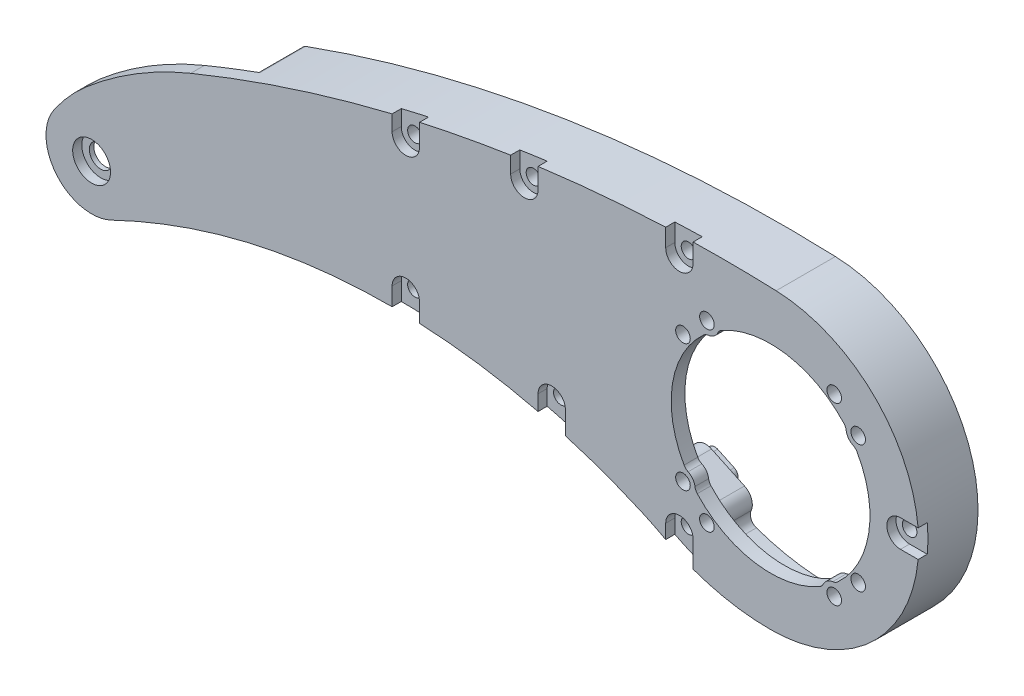
SolidWorks part; units mm, degrees
material "6061-T6 (SS)"
ref_plane "前视基准面" through (0, 0, 0) normal (0, 0, 1) x (1, 0, 0)
ref_plane "上视基准面" through (0, 0, 0) normal (0, 1, 0) x (1, 0, 0)
ref_plane "右视基准面" through (0, 0, 0) normal (1, 0, 0) x (0, 0, -1)
other "Configuration Table"
sketch "草图1" plane through (0, 0, 0) normal (0, 0, 1) x (1, 0, 0)
  line L0 (-74.3846, 0) -> (17.4339, 0) construction
  line L1 (0, 31.8895) -> (0, -25.7876) construction
  line L2 (0, 0) -> (19.2142, 13.9599) construction
  line L3 (0, 0) -> (13.9599, 19.2142) construction
  line L4 (0, 0) -> (-148.9161, -18) construction
  line L6 (0, 0) -> (-1.2281, 22.9672) construction
  line L8 (-1.2281, 22.9672) -> (-150.1441, 4.9672) construction
  line L9 (-150.1441, 4.9672) -> (-148.9161, -18) construction
  line L10 (-148.9161, -18) -> (-97.5528, -158.9319)
  line L12 (0, 0) -> (-103.1063, -167.9797) construction
  arc A116 (16.0762, 14.724) -> (-10.7394, 18.9712) centre (0, 0) ccw
  circle A117 centre (0, 0) radius 23.75 construction
  circle A118 centre (19.2142, 13.9599) radius 1.6
  circle A119 centre (13.9599, 19.2142) radius 1.6
  circle A120 centre (19.2142, -13.9599) radius 1.6
  circle A121 centre (13.9599, -19.2142) radius 1.6
  circle A122 centre (-13.9599, -19.2142) radius 1.6
  circle A123 centre (-19.2142, -13.9599) radius 1.6
  circle A124 centre (-19.2142, 13.9599) radius 1.6
  circle A125 centre (-13.9599, 19.2142) radius 1.6
  arc A126 (0, -32.5) -> (1.2171, 32.4772) centre (0, 0) ccw
  arc A127 (-157.1671, -12.3502) -> (-144.5702, -27.0063) centre (-148.9161, -18) ccw
  arc A134 (-28.3708, -24.2609) -> (-127.3793, -19.9637) centre (-83.3912, -149.2082) ccw
  arc A135 (-127.3793, -19.9637) -> (-144.5702, -27.0063) centre (-78.0965, -164.7651) ccw
  arc A136 (1.2171, 32.4772) -> (-127.1723, 9.5805) centre (-10.2849, -274.4361) ccw
  arc A138 (-23.6381, -26.5665) -> (-28.3708, -24.2609) centre (-55.9067, -86.7929) ccw
  arc A139 (0, -32.5) -> (-23.6381, -26.5665) centre (0, 17.5518) cw
  arc A140 (16.5853, 13.6255) -> (18.0838, 11.5631) centre (19.2142, 13.9599) ccw
  arc A141 (16.5853, 13.6255) -> (16.0762, 14.724) centre (14.6013, 13.3732) ccw
  arc A142 (18.0838, 11.5631) -> (18.9712, 10.7394) centre (17.2307, 9.7541) cw
  arc A143 (11.5631, -18.0838) -> (10.7394, -18.9712) centre (9.7541, -17.2307) cw
  arc A144 (13.6255, -16.5853) -> (11.5631, -18.0838) centre (13.9599, -19.2142) ccw
  arc A145 (13.6255, -16.5853) -> (14.724, -16.0762) centre (13.3732, -14.6013) ccw
  arc A146 (-18.0838, -11.5631) -> (-18.9712, -10.7394) centre (-17.2307, -9.7541) cw
  arc A147 (-16.5853, -13.6255) -> (-18.0838, -11.5631) centre (-19.2142, -13.9599) ccw
  arc A148 (-16.5853, -13.6255) -> (-16.0762, -14.724) centre (-14.6013, -13.3732) ccw
  arc A149 (-11.5631, 18.0838) -> (-10.7394, 18.9712) centre (-9.7541, 17.2307) cw
  arc A150 (-13.6255, 16.5853) -> (-11.5631, 18.0838) centre (-13.9599, 19.2142) ccw
  arc A151 (-13.6255, 16.5853) -> (-14.724, 16.0762) centre (-13.3732, 14.6013) ccw
  arc A152 (-16.0762, -14.724) -> (10.7394, -18.9712) centre (0, 0) ccw
  arc A153 (14.724, -16.0762) -> (18.9712, 10.7394) centre (0, 0) ccw
  arc A154 (-14.724, 16.0762) -> (-18.9712, -10.7394) centre (0, 0) ccw
  arc A155 (-127.1723, 9.5805) -> (-150.1438, -4.5112) centre (-94.9478, -68.7195) ccw
  arc A156 (-150.1438, -4.5112) -> (-157.1671, -12.3502) centre (-123.7132, -35.2574) ccw
  arc A157 (11.5631, 18.0838) -> (10.7394, 18.9712) centre (9.7541, 17.2307) ccw
  arc A158 (11.5631, 18.0838) -> (13.6255, 16.5853) centre (13.9599, 19.2142) ccw
  arc A159 (13.6255, 16.5853) -> (14.724, 16.0762) centre (13.3732, 14.6013) cw
  arc A160 (16.5853, -13.6255) -> (16.0762, -14.724) centre (14.6013, -13.3732) cw
  arc A161 (18.0838, -11.5631) -> (16.5853, -13.6255) centre (19.2142, -13.9599) ccw
  arc A162 (18.0838, -11.5631) -> (18.9712, -10.7394) centre (17.2307, -9.7541) ccw
  arc A163 (-13.6255, -16.5853) -> (-14.724, -16.0762) centre (-13.3732, -14.6013) cw
  arc A164 (-11.5631, -18.0838) -> (-13.6255, -16.5853) centre (-13.9599, -19.2142) ccw
  arc A165 (-11.5631, -18.0838) -> (-10.7394, -18.9712) centre (-9.7541, -17.2307) ccw
  arc A166 (-16.5853, 13.6255) -> (-16.0762, 14.724) centre (-14.6013, 13.3732) cw
  arc A167 (-18.0838, 11.5631) -> (-16.5853, 13.6255) centre (-19.2142, 13.9599) ccw
  arc A168 (-18.0838, 11.5631) -> (-18.9712, 10.7394) centre (-17.2307, 9.7541) ccw
  arc A169 (18.9712, 10.7394) -> (16.0762, 14.724) centre (0, 0) ccw
  arc A170 (-10.7394, 18.9712) -> (-14.724, 16.0762) centre (0, 0) ccw
  arc A171 (10.7394, -18.9712) -> (14.724, -16.0762) centre (0, 0) ccw
  point P27 (0, 0)
  point P73 (0, 0)
  point P83 (0, 0)
  point P105 (0, 0)
  dimension "D1" = 43.6
  dimension "D3" = 36
  dimension "D4" = 3.2
  dimension "D2" = 47.5
  dimension "D6" = 3.2
  dimension "D8" = 65
  dimension "D15" = 20
  dimension "D16" = 5.3
  dimension "D17" = 2
  dimension "D5" = 18
  dimension "D9" = 18
  dimension "D10" = 150
  dimension "D11" = 23
  dimension "D12" = 150
  dimension "D13" = 103.132
  dimension "D14" = 51.566
  dimension "D19" = 2
  dimension "D7" = 4
  dimension "D18" = 4
  dimension "D20" = 4
extrude "凸台-拉伸1" add sketch "草图1" along normal blind 3 contours A135 A134 A138 A126 A127 A125 A124 A123 A122 A121 A120 A119 A118 A116 | A149 A170 A151 A150 | A142 A169 A141 A140 | A143 A171 A145 A144 region at (17.4035, 12.6444, 0) region at (-12.6444, 17.4035, 0) region at (12.6444, -17.4035, 0) region at (-60.0693, 1.6089, 0)
sketch "草图2" plane through (0, 0, 0) normal (0, 0, -1) x (-1, 0, 0)
  line L0 (-28.5, 0) -> (0, 0) construction
  line L2 (0, 0) -> (-20.7479, 9.926) construction
  line L3 (-20.7479, 9.926) -> (128.1682, -8.074) construction
  line L4 (128.1682, -8.074) -> (148.9161, -18) construction
  line L5 (148.9161, -18) -> (265.6411, -112.2087) construction
  line L7 (-13.9568, 11.6234) -> (123.0533, -4.9375) construction
  line L9 (-14.5568, 6.6595) -> (122.4533, -9.9014) construction
  line L11 (19.8643, 25.54) -> (27.8561, 25.1781)
  line L13 (18.7235, -21.0787) -> (25.9631, -17.6745)
  line L16 (53.5282, 22.5613) -> (61.4287, 21.3032)
  line L17 (79.2716, 17.6568) -> (87.0322, 15.7143)
  line L19 (80.013, -5.7241) -> (88.0129, -5.7588)
  line L20 (47.3274, -10.2892) -> (55.1237, -8.4956)
  line L21 (0, 0) -> (148.9161, -18) construction
  arc A111 (-1.1422, 30.4786) -> (-30.0624, 5.1483) centre (0, 0) ccw
  arc A112 (0, -30.5) -> (16.1065, -27.7202) centre (0, 17.5518) ccw
  arc A114 (75.0886, -10.9322) -> (61.0732, -12.4928) centre (83.3912, -149.2082) ccw
  arc A116 (144.5702, -27.0063) -> (157.1671, -12.3502) centre (148.9161, -18) ccw
  arc A118 (157.1671, -12.3502) -> (150.1438, -4.5112) centre (123.7132, -35.2574) ccw
  arc A119 (127.1723, 9.5805) -> (-1.2171, 32.4772) centre (10.2849, -274.4361) ccw
  arc A120 (-1.2171, 32.4772) -> (0, -32.5) centre (0, 0) ccw
  arc A121 (-1.0673, 28.48) -> (0, -28.5) centre (0, 0) ccw construction
  arc A122 (0, -32.5) -> (23.6381, -26.5665) centre (0, 17.5518) ccw
  arc A123 (28.3708, -24.2609) -> (23.6381, -26.5665) centre (55.9067, -86.7929) ccw
  arc A124 (127.3793, -19.9637) -> (28.3708, -24.2609) centre (83.3912, -149.2082) ccw
  arc A125 (144.5702, -27.0063) -> (127.3793, -19.9637) centre (78.0965, -164.7651) ccw
  arc A126 (144.5702, -27.0063) -> (157.1671, -12.3502) centre (148.9161, -18) ccw
  arc A128 (127.1723, 9.5805) -> (-1.2171, 32.4772) centre (10.2849, -274.4361) ccw
  arc A129 (-1.2171, 32.4772) -> (0, -32.5) centre (0, 0) ccw
  arc A130 (0, -32.5) -> (23.6381, -26.5665) centre (0, 17.5518) ccw
  arc A131 (28.3708, -24.2609) -> (23.6381, -26.5665) centre (55.9067, -86.7929) ccw
  arc A132 (127.3793, -19.9637) -> (28.3708, -24.2609) centre (83.3912, -149.2082) ccw
  arc A133 (144.5702, -27.0063) -> (127.3793, -19.9637) centre (78.0965, -164.7651) ccw
  arc A134 (0, -28.5) -> (21.749, -23.0407) centre (0, 17.5518) ccw construction
  arc A135 (26.7587, -20.6001) -> (21.749, -23.0407) centre (55.9067, -86.7929) ccw construction
  arc A136 (128.6681, -16.177) -> (26.7587, -20.6001) centre (83.3912, -149.2082) ccw construction
  arc A137 (146.3086, -23.4038) -> (128.6681, -16.177) centre (78.0965, -164.7651) ccw construction
  arc A138 (146.3086, -23.4038) -> (153.7238, -14.4104) centre (148.9161, -18) ccw construction
  arc A139 (153.7238, -14.4104) -> (126.0955, 5.6977) centre (120.8678, -30.5198) ccw construction
  arc A140 (126.0955, 5.6977) -> (-1.0673, 28.48) centre (10.2849, -274.4361) ccw construction
  arc A141 (-28.3421, -2.9958) -> (-28.3421, 2.9958) centre (-28.5, 0) ccw
  arc A142 (-28.3421, 2.9958) -> (-30.0624, 5.1483) centre (-28.2451, 4.837) cw
  arc A143 (-28.3421, -2.9958) -> (-30.0624, -5.1483) centre (-28.2451, -4.837) ccw
  arc A144 (-30.0624, -5.1483) -> (0, -30.5) centre (0, 0) ccw
  circle A145 centre (-28.5, 0) radius 1.6
  arc A146 (-1.1422, 30.4786) -> (0, -30.5) centre (0, 0) ccw construction
  circle A147 centre (-20.7479, 9.926) radius 7 construction
  circle A148 centre (128.1682, -8.074) radius 6 construction
  arc A149 (17.0011, 28.6182) -> (19.8643, 25.54) centre (20, 28.5369) ccw
  arc A150 (27.8561, 25.1781) -> (30.9858, 27.985) centre (27.9918, 28.175) ccw
  arc A151 (17.0011, 28.6182) -> (15.0491, 30.6555) centre (15.0181, 28.672) ccw
  arc A152 (30.9858, 27.985) -> (33.1139, 29.8374) centre (32.9655, 27.8593) cw
  arc A153 (15.0491, 30.6555) -> (-1.1422, 30.4786) centre (10.2849, -274.4361) ccw
  circle A154 centre (20, 28.5369) radius 1.6
  arc A155 (126.6313, 7.6402) -> (-1.1422, 30.4786) centre (10.2849, -274.4361) ccw construction
  arc A156 (17.2617, -25.019) -> (18.7235, -21.0787) centre (20, -23.7935) cw
  arc A157 (25.9631, -17.6745) -> (30.0023, -19.2201) centre (27.2396, -20.3894) cw
  circle A158 centre (20, -23.7935) radius 1.6
  arc A159 (17.2617, -25.019) -> (16.1065, -27.7202) centre (15.4362, -25.8359) cw
  arc A160 (30.0023, -19.2201) -> (32.6241, -20.3211) centre (31.8778, -18.4263) ccw
  circle A161 centre (54, 25.524) radius 1.6
  arc A162 (27.5648, -22.4305) -> (22.6935, -24.8036) centre (55.9067, -86.7929) ccw construction
  arc A163 (0, -30.5) -> (22.6935, -24.8036) centre (0, 17.5518) ccw construction
  arc A164 (128.0237, -18.0703) -> (27.5648, -22.4305) centre (83.3912, -149.2082) ccw construction
  arc A165 (51.0293, 25.9419) -> (53.5282, 22.5613) centre (54, 25.524) ccw
  arc A166 (61.4287, 21.3032) -> (64.8541, 23.7404) centre (61.9005, 24.2659) ccw
  arc A167 (51.0293, 25.9419) -> (49.3187, 28.1856) centre (49.0649, 26.2183) ccw
  arc A168 (64.8541, 23.7404) -> (67.177, 25.3419) centre (66.8071, 23.393) cw
  arc A169 (49.3187, 28.1856) -> (33.1139, 29.8374) centre (10.2849, -274.4361) ccw
  circle A170 centre (80, 20.567) radius 1.6
  arc A171 (77.077, 21.2425) -> (79.2716, 17.6568) centre (80, 20.567) ccw
  arc A172 (87.0322, 15.7143) -> (90.6571, 17.8435) centre (87.7606, 18.6246) ccw
  arc A173 (77.077, 21.2425) -> (75.5687, 23.6269) centre (75.1443, 21.6892) ccw
  arc A175 (75.5687, 23.6269) -> (67.177, 25.3419) centre (10.2849, -274.4361) ccw
  circle A176 centre (48, -13.2128) radius 1.6
  circle A177 centre (80, -8.7241) radius 1.6
  arc A178 (45.1049, -13.9993) -> (47.3274, -10.2892) centre (48, -13.2128) cw
  arc A180 (45.1049, -13.9993) -> (43.7228, -16.4844) centre (43.1397, -14.5332) cw
  arc A182 (43.7228, -16.4844) -> (32.6241, -20.3211) centre (83.3912, -149.2082) ccw
  arc A183 (77.0018, -8.8285) -> (80.013, -5.7241) centre (80, -8.7241) cw
  arc A184 (88.0129, -5.7588) -> (90.9961, -8.9104) centre (87.9999, -8.7587) cw
  arc A185 (77.0018, -8.8285) -> (75.0886, -10.9322) centre (74.9666, -8.8993) cw
  arc A186 (90.9961, -8.9104) -> (92.8569, -11.0069) centre (92.9935, -9.0116) ccw
  arc A187 (107.3459, -12.77) -> (108.9673, -15.1002) centre (107, -14.7399) cw
  arc A188 (145.4394, -25.205) -> (128.0237, -18.0703) centre (78.0965, -164.7651) ccw construction
  arc A189 (128.0237, -18.0703) -> (27.5648, -22.4305) centre (83.3912, -149.2082) ccw
  arc A190 (145.4394, -25.205) -> (155.4422, -13.3729) centre (148.9161, -18) ccw construction
  arc A191 (75.5687, 23.6269) -> (93.1109, 19.2362) centre (10.2849, -274.4361) cw construction
  arc A192 (90.6571, 17.8435) -> (93.1109, 19.2362) centre (92.5724, 17.327) cw
  arc A193 (155.4422, -13.3729) -> (126.6313, 7.6402) centre (120.8678, -30.5198) ccw construction
  arc A194 (15.0491, 30.6555) -> (33.1139, 29.8374) centre (10.2849, -274.4361) cw construction
  arc A195 (49.3187, 28.1856) -> (67.177, 25.3419) centre (10.2849, -274.4361) cw construction
  arc A196 (93.1109, 19.2362) -> (114.3181, 12.4099) centre (10.2849, -274.4361) cw
  arc A197 (114.3181, 12.4099) -> (116.8779, 13.6021) centre (115, 14.2901) ccw
  arc A198 (55.1237, -8.4956) -> (58.7441, -10.8615) centre (55.7963, -11.4192) cw
  arc A199 (58.7441, -10.8615) -> (61.0732, -12.4928) centre (60.745, -10.4829) ccw
  arc A201 (27.5648, -22.4305) -> (22.6935, -24.8036) centre (55.9067, -86.7929) ccw
  arc A202 (0, -30.5) -> (22.6935, -24.8036) centre (0, 17.5518) ccw
  arc A203 (-1.1422, 30.4786) -> (0, -30.5) centre (0, 0) ccw
  arc A204 (126.4111, 7.731) -> (-1.1422, 30.4786) centre (10.2849, -274.4361) ccw
  arc A205 (148.8401, -6.0279) -> (126.4111, 7.731) centre (94.9478, -68.7195) ccw
  arc A206 (155.5169, -13.4802) -> (148.8401, -6.0279) centre (123.7132, -35.2574) ccw
  arc A207 (157.1671, -12.3502) -> (127.1723, 9.5805) centre (120.8678, -30.5198) ccw construction
  arc A208 (157.1671, -12.3502) -> (150.1438, -4.5112) centre (123.7132, -35.2574) ccw
  arc A209 (150.1438, -4.5112) -> (127.1723, 9.5805) centre (94.9478, -68.7195) ccw
  arc A210 (150.1438, -4.5112) -> (127.1723, 9.5805) centre (94.9478, -68.7195) ccw
  arc A211 (145.4394, -25.205) -> (155.5169, -13.4802) centre (148.9161, -18) ccw
  arc A212 (145.4394, -25.205) -> (128.0237, -18.0703) centre (78.0965, -164.7651) ccw
  point P113 (16.5105, -418.9921)
  arc M20 (127.1723, 9.5805) -> (-1.2171, 32.4772) centre (10.2849, -274.4361) ccw
  arc M21 (-1.2171, 32.4772) -> (0, -32.5) centre (0, 0) ccw
  arc M22 (0, -32.5) -> (23.6381, -26.5665) centre (0, 17.5518) ccw
  arc M23 (23.6381, -26.5665) -> (28.3708, -24.2609) centre (55.9067, -86.7929) cw
  arc M24 (28.3708, -24.2609) -> (127.3793, -19.9637) centre (83.3912, -149.2082) cw
  arc M25 (127.3793, -19.9637) -> (144.5702, -27.0063) centre (78.0965, -164.7651) cw
  dimension "D7" = 150
  dimension "D9" = 14
  dimension "D11" = 12
  dimension "D12" = 150
  dimension "D13" = 8
  dimension "D10" = 2.5
  dimension "D8" = 166.66
  dimension "D14" = 20
  dimension "D15" = 8
  dimension "D16" = 8
  dimension "D17" = 8
  dimension "D18" = 54
  dimension "D19" = 80
  dimension "D20" = 8
  dimension "D21" = 48
  dimension "D22" = 80
  dimension "D23" = 8
  dimension "D6" = 23
  dimension "D25" = 107
  dimension "D26" = 2
  dimension "D27" = 115
  dimension "D28" = 20
  dimension "D4" = 6
  dimension "D5" = 3.2
  dimension "D24" = 2
  dimension "D29" = 2
  dimension "D1" = 0
  dimension "D2" = 2
  dimension "D3" = 2
extrude "凸台-拉伸2" add sketch "草图2" along normal blind 10 contours M20 M21 M22 M23 M24 M25 | A152 A204 A151 A149 L11 A150 A154 | A168 A204 A167 A165 L16 A166 A161 | A192 A204 A173 A171 L17 A172 A170 | A189 A186 A184 L19 A183 A185 A177 | A199 A198 L20 A178 A180 A189 A176 | A159 A202 A201 A189 A160 A157 L13 A156 A158 | A142 A203 A143 A141 A145 region at (-24.5149, 27.9422, 0) region at (-6.9345, 32.3042, 0) region at (-58.4194, 24.4254, 0) region at (29.7748, 3.6145, 0) region at (-84.3067, 19.0872, 0) region at (-23.8926, -21.565, 0) region at (-52.3362, -11.8146, 0) region at (-84.5374, -8.3524, 0)
sketch "草图4" plane through (0, 0, -10) normal (0, 0, -1) x (-1, 0, 0)
  line L0 (20, 28.5369) -> (27.9918, 28.175) construction
  line L3 (61.9005, 24.2659) -> (54, 25.524) construction
  line L8 (80, 20.567) -> (87.7606, 18.6246) construction
  line L9 (20, -23.7935) -> (27.2396, -20.3894) construction
  line L10 (48, -13.2128) -> (55.7963, -11.4192) construction
  line L11 (80, -8.7241) -> (87.9999, -8.7587) construction
  line L12 (27.2396, -20.3894) -> (23.6198, -22.0915) construction
  line L15 (27.8779, -21.7468) -> (24.2581, -23.4489)
  line L24 (26.6013, -19.032) -> (22.9815, -20.734)
  line L27 (27.9918, 28.175) -> (23.9959, 28.356) construction
  line L30 (27.924, 26.6766) -> (23.9281, 26.8575)
  line L33 (28.0597, 29.6735) -> (24.0638, 29.8545)
  line L36 (61.9005, 24.2659) -> (57.9502, 24.8949) construction
  line L39 (87.7606, 18.6246) -> (83.8803, 19.5958) construction
  line L40 (87.3964, 17.1695) -> (83.5161, 18.1407)
  line L41 (88.1248, 20.0797) -> (84.2445, 21.0509)
  line L42 (87.9999, -8.7587) -> (84, -8.7414) construction
  line L43 (87.9934, -10.2587) -> (83.9935, -10.2414)
  line L44 (88.0064, -7.2587) -> (84.0065, -7.2414)
  line L45 (55.7963, -11.4192) -> (51.8982, -12.316) construction
  line L46 (56.1326, -12.881) -> (52.2345, -13.7778)
  line L47 (55.46, -9.9574) -> (51.5619, -10.8542)
  line L48 (61.6646, 22.7845) -> (57.7143, 23.4136)
  line L49 (62.1363, 25.7472) -> (58.1861, 26.3763)
  arc A24 (27.8779, -21.7468) -> (26.6013, -19.032) centre (27.2396, -20.3894) ccw
  arc A25 (22.9815, -20.734) -> (24.2581, -23.4489) centre (23.6198, -22.0915) ccw
  arc A26 (27.924, 26.6766) -> (28.0597, 29.6735) centre (27.9918, 28.175) ccw
  arc A27 (24.0638, 29.8545) -> (23.9281, 26.8575) centre (23.9959, 28.356) ccw
  arc A30 (87.3964, 17.1695) -> (88.1248, 20.0797) centre (87.7606, 18.6246) ccw
  arc A31 (84.2445, 21.0509) -> (83.5161, 18.1407) centre (83.8803, 19.5958) ccw
  arc A32 (87.9934, -10.2587) -> (88.0064, -7.2587) centre (87.9999, -8.7587) ccw
  arc A33 (84.0065, -7.2414) -> (83.9935, -10.2414) centre (84, -8.7414) ccw
  arc A34 (56.1326, -12.881) -> (55.46, -9.9574) centre (55.7963, -11.4192) ccw
  arc A35 (51.5619, -10.8542) -> (52.2345, -13.7778) centre (51.8982, -12.316) ccw
  arc A36 (61.6646, 22.7845) -> (62.1363, 25.7472) centre (61.9005, 24.2659) ccw
  arc A37 (58.1861, 26.3763) -> (57.7143, 23.4136) centre (57.9502, 24.8949) ccw
  point P12 (25.4297, -21.2404)
  point P18 (25.9939, 28.2655)
  point P24 (59.9253, 24.5804)
  point P30 (85.8204, 19.1102)
  point P36 (85.9999, -8.7501)
  point P42 (53.8473, -11.8676)
  dimension "D2" = 1.5
  dimension "D1" = 4
extrude "凸台-拉伸3" add sketch "草图4" along normal blind 2 contours L44 A33 L43 A32 | L33 A27 L30 A26 | L49 A37 L48 A36 | A30 L41 A31 L40 | A34 L47 A35 L46 | A24 L24 A25 L15 region at (-85.9999, -8.7501, -10)
sketch "草图5" plane through (0, 0, -10) normal (0, 0, -1) x (-1, 0, 0)
  circle A0 centre (80, -8.7241) radius 1.6 construction
  circle A2 centre (-28.5, 0) radius 1.6 construction
  circle A4 centre (-28.5, 0) radius 1.6
  circle A6 centre (54, 25.524) radius 1.6 construction
  circle A8 centre (80, 20.567) radius 1.6 construction
  circle A10 centre (80, -8.7241) radius 1.6
  circle A12 centre (48, -13.2128) radius 1.6 construction
  circle A14 centre (20, -23.7935) radius 1.6 construction
  circle A27 centre (20, 28.5369) radius 1.6 construction
  circle A28 centre (54, 25.524) radius 1.6
  circle A29 centre (80, 20.567) radius 1.6
  circle A31 centre (48, -13.2128) radius 1.6
  circle A32 centre (20, -23.7935) radius 1.6
  circle A33 centre (20, 28.5369) radius 1.6
extrude "切除-拉伸1" cut sketch "草图5" against normal up to next
sketch "草图10" plane through (0, 0, 0) normal (0, 0, -1) x (-1, 0, 0)
  circle A0 centre (148.9161, -18) radius 2.5
  dimension "D1" = 5
extrude "切除-拉伸4" cut sketch "草图10" against normal up to next
sketch "草图11" plane through (0, 0, 3) normal (0, 0, 1) x (1, 0, 0)
  circle A0 centre (-148.9161, -18) radius 4.15
  dimension "D1" = 8.3
extrude "切除-拉伸5" cut sketch "草图11" against normal blind 2
sketch "草图13" plane through (0, 0, 3) normal (0, 0, 1) x (1, 0, 0)
  line L0 (-83, 20.567) -> (-83, 23.9606)
  line L1 (-77, 20.567) -> (-77, 25.3591)
  line L2 (-57, 25.524) -> (-57, 29.1191)
  line L3 (-51, 25.524) -> (-51, 29.982)
  line L4 (-23, 28.5369) -> (-23, 32.4293)
  line L5 (-17, 28.5369) -> (-17, 32.6192)
  line L6 (-83, -8.7241) -> (-83, -12.6837)
  line L7 (-77, -8.7241) -> (-77, -12.8328)
  line L8 (-51, -13.2128) -> (-51, -16.5813)
  line L9 (-45, -13.2128) -> (-45, -18.1922)
  line L10 (-23, -23.7935) -> (-23, -26.9025)
  line L11 (-17, -23.7935) -> (-17, -29.5246)
  line L12 (28.5, 3) -> (32.3612, 3)
  line L13 (28.5, -3) -> (32.3612, -3)
  line L14 (28.5, 3) -> (28.5, -3) construction
  arc A0 (-83, 20.567) -> (-77, 20.567) centre (-80, 20.567) ccw
  arc A1 (-57, 25.524) -> (-51, 25.524) centre (-54, 25.524) ccw
  arc A2 (-23, 28.5369) -> (-17, 28.5369) centre (-20, 28.5369) ccw
  arc A3 (28.5, 3) -> (28.5, -3) centre (28.5, 0) ccw
  arc A5 (-45, -13.2128) -> (-51, -13.2128) centre (-48, -13.2128) ccw
  arc A7 (-23.6381, -26.5665) -> (0, -32.5) centre (0, 17.5518) ccw construction
  arc A8 (1.2171, 32.4772) -> (-127.1723, 9.5805) centre (-10.2849, -274.4361) ccw construction
  arc A9 (-28.3708, -24.2609) -> (-127.3793, -19.9637) centre (-83.3912, -149.2082) ccw construction
  arc A10 (-23.6381, -26.5665) -> (0, -32.5) centre (0, 17.5518) ccw
  arc A11 (-23.6381, -26.5665) -> (-28.3708, -24.2609) centre (-55.9067, -86.7929) ccw construction
  arc A12 (0, -32.5) -> (1.2171, 32.4772) centre (0, 0) ccw construction
  arc A13 (1.2171, 32.4772) -> (-127.1723, 9.5805) centre (-10.2849, -274.4361) ccw
  arc A15 (0, -32.5) -> (1.2171, 32.4772) centre (0, 0) ccw
  arc A16 (-23.6381, -26.5665) -> (-28.3708, -24.2609) centre (-55.9067, -86.7929) ccw
  arc A18 (-17, -23.7935) -> (-23, -23.7935) centre (-20, -23.7935) ccw
  arc A19 (-28.3708, -24.2609) -> (-127.3793, -19.9637) centre (-83.3912, -149.2082) ccw
  arc A20 (-77, -8.7241) -> (-83, -8.7241) centre (-80, -8.7241) ccw
  circle M9 centre (28.5, 0) radius 1.6
  circle M10 centre (-54, 25.524) radius 1.6
  circle M11 centre (-80, 20.567) radius 1.6
  circle M12 centre (-80, -8.7241) radius 1.6
  circle M13 centre (-48, -13.2128) radius 1.6
  circle M14 centre (-20, -23.7935) radius 1.6
  circle M15 centre (-20, 28.5369) radius 1.6
  arc M17 (-127.3793, -19.9637) -> (-28.3708, -24.2609) centre (-83.3912, -149.2082) cw
  arc M19 (-23.6381, -26.5665) -> (0, -32.5) centre (0, 17.5518) ccw
  arc M20 (0, -32.5) -> (1.2171, 32.4772) centre (0, 0) ccw
  arc M21 (1.2171, 32.4772) -> (-127.1723, 9.5805) centre (-10.2849, -274.4361) ccw
  dimension "D1" = 6
  dimension "D2" = 6
  dimension "D3" = 3
  dimension "D4" = 6
extrude "切除-拉伸6" cut sketch "草图13" against normal blind 2 contours L9 A5 L8 M17 M13 | L11 A18 L10 M19 M14 | L12 L14 L13 M9 M20 | L14 A3 M9 | L4 A2 L5 M21 M15 | L2 A1 L3 M21 M10 | L0 A0 L1 M21 M11 | L7 A20 L6 M17 M12 region at (-79.9969, -12.6323, 3) region at (-47.9649, -17.2562, 3) region at (-20.0005, -28.2147, 3) region at (30.7421, 0, 3) region at (-19.9975, 32.4462, 3) region at (-53.9885, 29.4706, 3) region at (-82.9017, 22.2638, 3) region at (28.4329, 2.3, 3)
sketch "草图14" plane through (0, 0, 0) normal (0, 0, -1) x (-1, 0, 0)
  circle A0 centre (148.9161, -18) radius 10
  circle A1 centre (148.9161, -18) radius 7
  dimension "D1" = 14
  dimension "D2" = 20
extrude "凸台-拉伸4" add sketch "草图14" along normal blind 1.5
fillet "圆角1" radius 1 1 edges at (-116.8779, 13.6021, -5)
fillet "圆角2" radius 0.9 1 edges at (-108.9673, -15.1002, -5)
sketch "草图15" plane through (0, 0, -10) normal (0, 0, -1) x (-1, 0, 0)
  line L0 (0, 0) -> (148.9161, -18)
